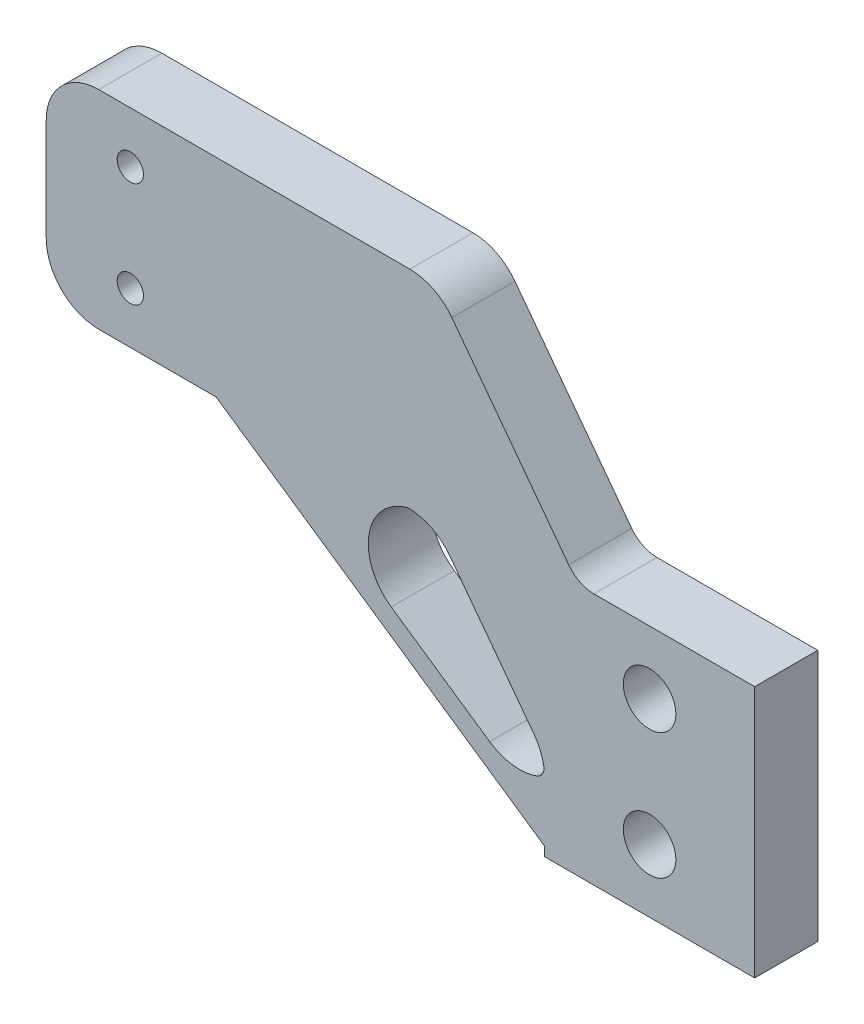
SolidWorks part; units mm, degrees
ref_plane "前视基准面" through (0, 0, 0) normal (0, 0, 1) x (1, 0, 0)
ref_plane "上视基准面" through (0, 0, 0) normal (0, 1, 0) x (1, 0, 0)
ref_plane "右视基准面" through (0, 0, 0) normal (1, 0, 0) x (0, 0, -1)
other "Configuration Table"
sketch "草图1" plane through (0, 0, 0) normal (0, 0, 1) x (1, 0, 0)
  line L0 (1.5, -1.9992) -> (12.6059, -16.8005)
  line L1 (30.3064, -32.6149) -> (30.3064, -42)
  line L2 (30.3064, -42) -> (10.3064, -42)
  line L3 (10.3064, -42) -> (10.3064, -41.1221)
  line L4 (9.3057, -32.3967) -> (1.3166, -21.7492)
  line L5 (-2.6828, -19.75) -> (-17.3882, -19.75)
  line L6 (-37.0936, -14.75) -> (-37.0936, -5)
  line L7 (-32.0936, 0) -> (-2.4993, 0)
  line L8 (-17.3882, -19.75) -> (10.3064, -38.6988)
  line L9 (15.0055, -18) -> (30.3064, -18)
  line L10 (30.3064, -18) -> (30.3064, -32.6149)
  line L11 (10.3064, -41.1221) -> (-20.93, -19.75)
  line L12 (10.3064, -38.6988) -> (10.3064, -35.3975)
  line L13 (-20.93, -19.75) -> (-32.0936, -19.75)
  circle A0 centre (20.3064, -36) radius 2.5
  circle A1 centre (20.3064, -24) radius 2.5
  arc A2 (15.0055, -18) -> (12.6059, -16.8005) centre (15.0055, -15) cw
  circle A3 centre (-29.0936, -4.875) radius 1.25
  circle A4 centre (-29.0936, -14.875) radius 1.25
  arc A5 (10.3064, -35.3975) -> (9.3057, -32.3967) centre (5.3064, -35.3975) ccw
  arc A6 (1.3166, -21.7492) -> (-2.6828, -19.75) centre (-2.6828, -24.75) ccw
  arc A7 (-32.0936, -19.75) -> (-37.0936, -14.75) centre (-32.0936, -14.75) cw
  arc A8 (-37.0936, -5) -> (-32.0936, 0) centre (-32.0936, -5) cw
  arc A9 (1.5, -1.9992) -> (-2.4993, 0) centre (-2.4993, -5) ccw
  point P17 (13.5059, -18)
  point P24 (10.3064, -33.7303)
  point P33 (0, 0)
  dimension "D5" = 5
  dimension "D6" = 5
  dimension "D9" = 3
  dimension "D11" = 2.5
  dimension "D12" = 2.5
  dimension "D17" = 5
  dimension "D18" = 5
  dimension "D1" = 20
  dimension "D2" = 18
  dimension "D3" = 8.2697
  dimension "D4" = 24
  dimension "D7" = 6
  dimension "D8" = 6
  dimension "D10" = 19.75
  dimension "D13" = 10
  dimension "D14" = 4.875
  dimension "D15" = 39.4
  dimension "D16" = 47.4
  dimension "D19" = 2
extrude "凸台-拉伸1" add sketch "草图1" along normal blind 6
fillet "圆角1" radius 5 2 edges at (10.3064, -38.6988, 3) (-17.3882, -19.75, 3)
fillet "圆角2" radius 1 1 edges at (10.3064, -35.3975, 3)
